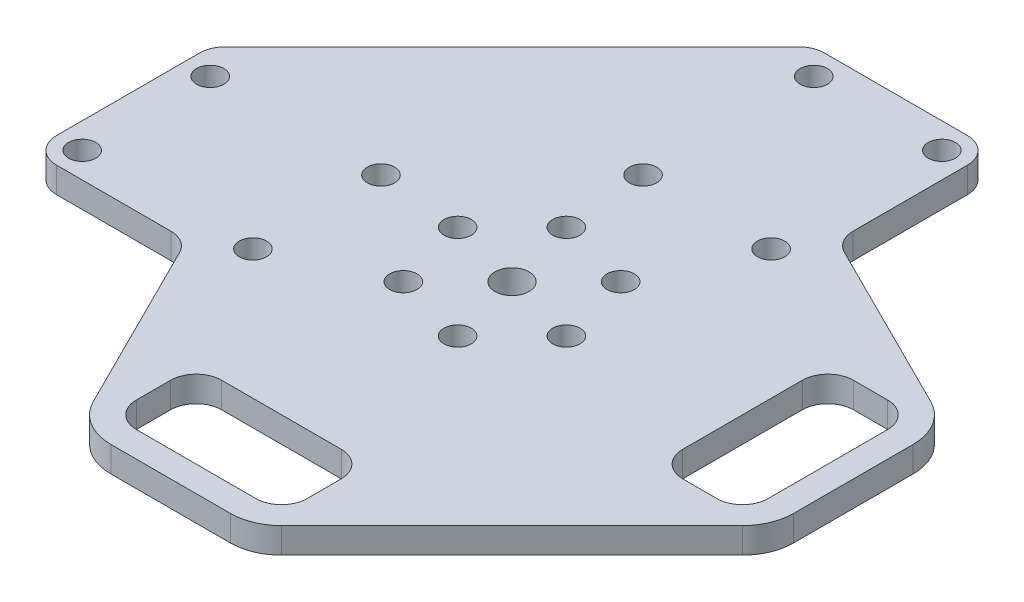
SolidWorks part; units mm, degrees
material "6061-T6 (SS)"
ref_plane "Front Plane" through (0, 0, 0) normal (0, 0, 1) x (1, 0, 0)
ref_plane "Top Plane" through (0, 0, 0) normal (0, 1, 0) x (1, 0, 0)
ref_plane "Right Plane" through (0, 0, 0) normal (1, 0, 0) x (0, 0, -1)
sketch "Sketch1" plane through (0, 0, 0) normal (0, 1, 0) x (1, 0, 0)
  line L1 (11.85, 18.5) -> (-3.15, 18.5)
  line L2 (11.85, 18.5) -> (11.85, 38.5)
  line L3 (11.85, 38.5) -> (-3.15, 38.5)
  line L4 (-3.15, 18.5) -> (-3.15, 38.5)
  line L5 (11.85, 18.5) -> (-3.15, 38.5) construction
  line L6 (11.85, 38.5) -> (-3.15, 18.5) construction
  line L7 (-18.5, -11.85) -> (-38.5, -11.85)
  line L8 (-18.5, -11.85) -> (-18.5, 3.15)
  line L9 (-18.5, 3.15) -> (-38.5, 3.15)
  line L10 (-38.5, -11.85) -> (-38.5, 3.15)
  line L11 (-18.5, -11.85) -> (-38.5, 3.15) construction
  line L12 (-18.5, 3.15) -> (-38.5, -11.85) construction
  line L13 (21.7, 15) -> (-13, 15)
  line L14 (21.7, 15) -> (21.7, 42)
  line L15 (21.7, 42) -> (-13, 42)
  line L16 (-13, 15) -> (-13, 42)
  line L17 (21.7, 15) -> (-13, 42) construction
  line L18 (21.7, 42) -> (-13, 15) construction
  line L19 (-15, -21.7) -> (-42, -21.7)
  line L20 (-15, -21.7) -> (-15, 13)
  line L21 (-15, 13) -> (-42, 13)
  line L22 (-42, -21.7) -> (-42, 13)
  line L23 (-15, -21.7) -> (-42, 13) construction
  line L24 (-15, 13) -> (-42, -21.7) construction
  line L25 (10, -37) -> (-10, -37)
  line L26 (10, -37) -> (10, -27)
  line L27 (10, -27) -> (-10, -27)
  line L28 (-10, -37) -> (-10, -27)
  line L29 (10, -37) -> (-10, -27) construction
  line L30 (10, -27) -> (-10, -37) construction
  line L31 (37, -10) -> (27, -10)
  line L32 (37, -10) -> (37, 10)
  line L33 (37, 10) -> (27, 10)
  line L34 (27, -10) -> (27, 10)
  line L35 (37, -10) -> (27, 10) construction
  line L36 (37, 10) -> (27, -10) construction
  circle A0 centre (0, 0) radius 2
  circle A1 centre (0, 0) radius 9
  circle A2 centre (0, 0) radius 12.7
  point P3 (4.35, 28.5)
  point P8 (-28.5, -4.35)
  point P15 (0, -32)
  point P16 (-28.5, -4.35)
  point P17 (4.35, 28.5)
  point P30 (32, 0)
  point P35 (0, 0)
  point P36 (0, 0)
  dimension "D1" = 4
  dimension "D4" = 18
  dimension "D11" = 25.4
  dimension "D2" = 20
  dimension "D3" = 15
  dimension "D5" = 34.7
  dimension "D6" = 27
  dimension "D7" = 2
  dimension "D8" = 2
  dimension "D9" = 15
  dimension "D10" = 15
  dimension "D12" = 32
  dimension "D13" = 10
  dimension "D14" = 20
  dimension "D15" = 32
sketch "Sketch2" plane through (0, 0, 0) normal (0, 1, 0) x (1, 0, 0)
  line L0 (-6.15, 41.5) -> (14.85, 41.5)
  line L1 (14.85, 41.5) -> (14.85, 15.5)
  line L3 (-15.5, -14.85) -> (-41.5, -14.85)
  line L4 (-41.5, -14.85) -> (-41.5, 6.15)
  line L5 (-41.5, 6.15) -> (-6.15, 41.5)
  line L6 (-18.5, -11.85) -> (-38.5, -11.85) construction
  line L7 (11.85, 18.5) -> (11.85, 38.5) construction
  line L8 (11.85, 38.5) -> (-3.15, 38.5) construction
  line L9 (-38.5, -11.85) -> (-38.5, 3.15) construction
  line L10 (-18.5, -11.85) -> (-18.5, 3.15) construction
  line L11 (11.85, 18.5) -> (-3.15, 18.5) construction
  line L12 (-18.5, 3.15) -> (-38.5, 3.15) construction
  line L13 (-3.15, 18.5) -> (-3.15, 38.5) construction
  line L14 (-15.5, -14.85) -> (0.9826, -13.6647)
  line L15 (14.85, 15.5) -> (13.6647, -0.9826)
  circle A1 centre (0, 0) radius 12.7 construction
  arc A3 (0.9826, -13.6647) -> (13.6647, -0.9826) centre (0, 0) ccw
  dimension "D1" = 1
  dimension "D2" = 3
  dimension "D3" = 3
  dimension "D4" = 3
  dimension "D5" = 3
  dimension "D6" = 3
  dimension "D7" = 3
  dimension "D8" = 3
  dimension "D9" = 3
extrude "Boss-Extrude1" add sketch "Sketch2" along normal blind 3
hole_wizard "M3 Clearance Hole1" positions "Sketch3" profile "Sketch4" hole size "M3" standard "ANSI Metric" end condition up to next
sketch "Sketch3" plane through (0, 3, 0) normal (0, 1, 0) x (1, 0, 0)
  point P0 (-38.5, 3.15)
  point P3 (-18.5, 3.15)
  point P6 (-18.5, -11.85)
  point P9 (-38.5, -11.85)
  point P12 (-3.15, 18.5)
  point P15 (-3.15, 38.5)
  point P18 (11.85, 38.5)
  point P21 (11.85, 18.5)
sketch "Sketch4" plane through (-38.5, 3, -3.15) normal (1, 0, 0) x (0, 0, 1)
  line L0 (0, 0) -> (0, 3)
  line L1 (0, 3) -> (1.6, 3)
  line L2 (1.6, 3) -> (1.6, 0)
  line L5 (1.6, 0) -> (0, 0)
  line L11 (0, -6.35) -> (0, 107.95) construction
  dimension "Thru Hole Dia." = 3.2
  dimension "Thru Hole Depth" = 3
hole_wizard "M3 Clearance Hole2" positions "Sketch5" profile "Sketch6" hole size "M3" standard "ANSI Metric" end condition up to next
sketch "Sketch5" plane through (0, 3, 0) normal (0, 1, 0) x (1, 0, 0)
  line L4 (-8.6933, 2.3294) -> (-2.3294, 8.6933) construction
  line L5 (0, 0) -> (-5.5114, 5.5114) construction
  line L7 (-1000, 0) -> (49000, 0) construction
  circle A0 centre (0, 0) radius 9 construction
  point P23 (-2.3294, 8.6933)
  point P46 (6.364, 6.364)
  point P47 (8.6933, -2.3294)
  point P48 (2.3294, -8.6933)
  point P49 (-6.364, -6.364)
  point P50 (-8.6933, 2.3294)
  dimension "D1" = 45
  dimension "D2" = 6
sketch "Sketch6" plane through (-2.3294, 3, -8.6933) normal (1, 0, 0) x (0, 0, 1)
  line L0 (0, 0) -> (0, 3)
  line L1 (0, 3) -> (1.6, 3)
  line L2 (1.6, 3) -> (1.6, 0)
  line L5 (1.6, 0) -> (0, 0)
  line L11 (0, -6.35) -> (0, 107.95) construction
  dimension "Thru Hole Dia." = 3.2
  dimension "Thru Hole Depth" = 3
hole_wizard "Ø4.0 (4) Diameter Hole1" positions "Sketch7" profile "Sketch8" hole size "Ø4.0" standard "ANSI Metric" end condition up to next
sketch "Sketch7" plane through (0, 3, 0) normal (0, 1, 0) x (1, 0, 0)
  point P0 (0, 0)
sketch "Sketch8" plane through (0, 3, 0) normal (1, 0, 0) x (0, 0, 1)
  line L0 (0, 0) -> (0, 3)
  line L1 (0, 3) -> (2, 3)
  line L2 (2, 3) -> (2, 0)
  line L5 (2, 0) -> (0, 0)
  line L11 (0, -6.35) -> (0, 107.95) construction
  dimension "Thru Hole Dia." = 4
  dimension "Thru Hole Depth" = 3
ref_plane "Plane1" through (0, 0, 0) normal (-0.7071, 0, 0.7071) x (0.7071, 0, 0.7071)
sketch "Sketch11" plane through (0, 3, 0) normal (0, 1, 0) x (1, 0, 0)
  line L1 (7, -37) -> (-7, -37)
  line L2 (10, -34) -> (10, -30)
  line L3 (7, -27) -> (-7, -27)
  line L4 (-10, -34) -> (-10, -30)
  line L5 (10, -37) -> (-10, -27) construction
  line L6 (10, -27) -> (-10, -37) construction
  arc A0 (7, -37) -> (10, -34) centre (7, -34) ccw
  arc A1 (-7, -37) -> (-10, -34) centre (-7, -34) cw
  arc A2 (10, -30) -> (7, -27) centre (7, -30) ccw
  arc A3 (-7, -27) -> (-10, -30) centre (-7, -30) ccw
  point P0 (0, -32)
  dimension "D1" = 3
  dimension "D2" = 10
  dimension "D3" = 20
  dimension "D4" = 32
extrude "Extrude-Thin1" add sketch "Sketch11" against normal up to surface (3 mm away) separate body thin up to face at (0, 0, 2) thin type one direction wall 3
sketch "Sketch12" plane through (0, 3, 0) normal (0, 1, 0) x (1, 0, 0)
  line L0 (-12.3688, -36.6789) -> (-28.5, -4.35) construction
  line L1 (11.2426, -38.2426) -> (24.7426, -24.7426)
  line L2 (-38.8909, 38.8909) -> (38.8909, -38.8909) construction
  line L5 (24.7426, -24.7426) -> (9.6874, -9.6874)
  line L6 (-41.5, -14.85) -> (-15.5, -14.85) construction
  line L7 (-15.5, -14.85) -> (0.9826, -13.6647) construction
  line L8 (-23.2608, -14.85) -> (-15.5, -14.85)
  line L9 (-15.5, -14.85) -> (0.9826, -13.6647)
  line L10 (-12.3688, -36.6789) -> (-23.2608, -14.85)
  line L15 (13, -34) -> (13, -30)
  line L16 (7, -24) -> (-7, -24)
  line L17 (-13, -30) -> (-13, -34)
  line L18 (-7, -40) -> (7, -40)
  line L19 (13, -34) -> (13, -30)
  line L20 (7, -24) -> (-7, -24)
  line L21 (-13, -30) -> (-13, -34)
  arc A0 (-13, -34) -> (-7, -40) centre (-7, -34) ccw construction
  arc A1 (7, -40) -> (13, -34) centre (7, -34) ccw construction
  arc A4 (0.9826, -13.6647) -> (13.6647, -0.9826) centre (0, 0) ccw construction
  arc A5 (0.9826, -13.6647) -> (9.6874, -9.6874) centre (0, 0) ccw
  arc A10 (7, -40) -> (13, -34) centre (7, -34) ccw
  arc A11 (13, -30) -> (7, -24) centre (7, -30) ccw
  arc A12 (-7, -24) -> (-13, -30) centre (-7, -30) ccw
  arc A13 (-13, -34) -> (-7, -40) centre (-7, -34) ccw
  arc A14 (11.2426, -38.2426) -> (13, -34) centre (7, -34) ccw
  arc A15 (13, -30) -> (7, -24) centre (7, -30) ccw
  arc A16 (-7, -24) -> (-13, -30) centre (-7, -30) ccw
  arc A17 (-13, -34) -> (-12.3688, -36.6789) centre (-7, -34) ccw
  dimension "D1" = 0
extrude "Boss-Extrude4" add sketch "Sketch12" against normal up to surface (3 mm away) up to face at (0, 0, 2)
mirror "Mirror4" about plane through (0, 0, 0) normal (-0.7071, 0, 0.7071) of bodies 108
fillet "Fillet4" radius 3 6 edges at (14.85, 1.5, -41.5) (-6.15, 1.5, -41.5) (-41.5, 1.5, -6.15) (-41.5, 1.5, 14.85) (14.85, 1.5, -23.2608) (-23.2608, 1.5, 14.85)
